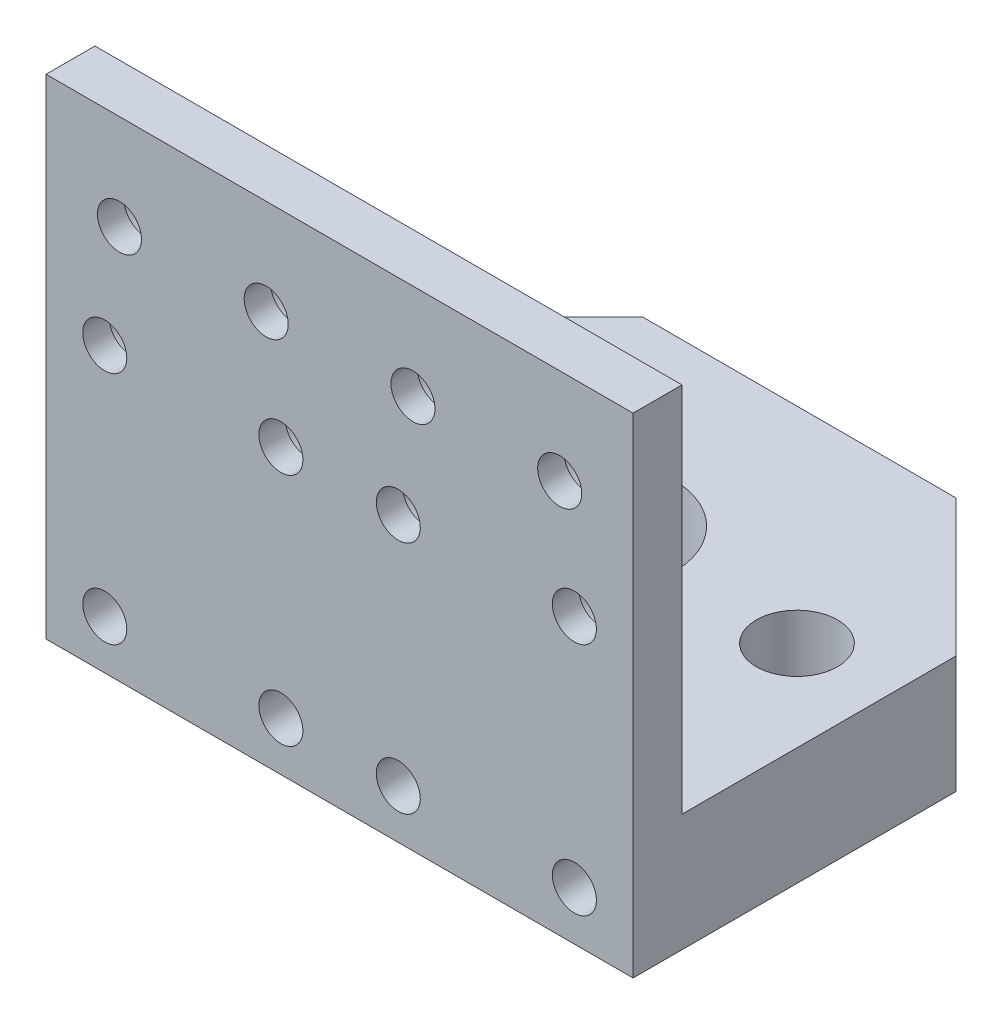
SolidWorks part; units mm, degrees
ref_plane "Front Plane" through (0, 0, 0) normal (0, 0, 1) x (1, 0, 0)
ref_plane "Top Plane" through (0, 0, 0) normal (0, 1, 0) x (1, 0, 0)
ref_plane "Right Plane" through (0, 0, 0) normal (1, 0, 0) x (0, 0, -1)
sketch "Sketch2" plane through (0, 0, 0) normal (1, 0, 0) x (0, 0, -1)
  line L23 (15.5, -57) -> (10.5, -57)
  line L24 (15.5, -57) -> (15.5, -7)
  line L25 (15.5, -7) -> (10.5, -7)
  line L26 (10.5, -57) -> (10.5, -7)
  dimension "D1" = 15.5
  dimension "D2" = 50
  dimension "D3" = 7
  dimension "D4" = 10.5
extrude "Boss-Extrude1" add sketch "Sketch2" along normal blind 30 and the other way blind 30 contours L24 L23 L26 L25
sketch "Sketch3" plane through (0, 0, -15.5) normal (0, 0, -1) x (-1, 0, 0)
  line L0 (30, -57) -> (30, -7) construction
  line L1 (-30, -57) -> (30, -57)
  line L2 (-30, -57) -> (-30, -45)
  line L3 (-30, -45) -> (30, -45)
  line L4 (30, -57) -> (30, -45)
  dimension "D1" = 12
extrude "Boss-Extrude2" add sketch "Sketch3" along normal blind 42
sketch "Sketch4" plane through (0, 0, -10.5) normal (0, 0, 1) x (1, 0, 0)
  line L0 (-30, -57) -> (-30, -7) construction
  line L1 (-30, -7) -> (30, -7) construction
  circle A0 centre (-22.5, -16.75) radius 2.25
  circle A1 centre (-7.5, -16.75) radius 2.25
  circle A2 centre (7.5, -16.75) radius 2.25
  circle A3 centre (22.5, -16.75) radius 2.25
  dimension "D1" = 4.5
  dimension "D2" = 7.5
  dimension "D3" = 9.75
  dimension "D5" = 15
  dimension "D4" = 4
extrude "Cut-Extrude1" cut sketch "Sketch4" against normal up to next
sketch "Sketch6" plane through (0, 0, -15.5) normal (0, 0, -1) x (-1, 0, 0)
  circle A0 centre (-22.5, -16.75) radius 4
  circle A1 centre (-7.5, -16.75) radius 4
  circle A2 centre (7.5, -16.75) radius 4
  circle A3 centre (22.5, -16.75) radius 4
  dimension "D1" = 8
  dimension "D3" = 15
  dimension "D2" = 4
extrude "Cut-Extrude2" cut sketch "Sketch6" against normal blind 2.3
sketch "Sketch7" plane through (0, 0, -10.5) normal (0, 0, 1) x (1, 0, 0)
  line L0 (-30, -57) -> (30, -57) construction
  line L1 (-30, -57) -> (-30, -7) construction
  line L2 (0, -7) -> (0, -57) construction
  line L3 (-30, -7) -> (30, -7) construction
  circle A0 centre (-24, -52) radius 2.25
  circle A1 centre (-6, -52) radius 2.25
  circle A2 centre (-24, -28) radius 2.25
  circle A3 centre (-6, -28) radius 2.25
  circle A4 centre (6, -28) radius 2.25
  circle A5 centre (24, -28) radius 2.25
  circle A6 centre (6, -52) radius 2.25
  circle A7 centre (24, -52) radius 2.25
  dimension "D1" = 5
  dimension "D2" = 6
  dimension "D3" = 4.5
  dimension "D5" = 18
  dimension "D7" = 24
  dimension "D4" = 2
  dimension "D6" = 2
extrude "Cut-Extrude3" cut sketch "Sketch7" against normal up to surface (5 mm away) up to face at (22.5, -12.75, -15.5)
sketch "Sketch8" plane through (0, 0, -15.5) normal (0, 0, -1) x (-1, 0, 0)
  line L0 (0, -7) -> (0, -45) construction
  line L1 (30, -7) -> (-30, -7) construction
  line L2 (30, -45) -> (-30, -45) construction
  circle A0 centre (-24, -28) radius 4
  circle A1 centre (-6, -28) radius 4
  circle A2 centre (6, -28) radius 4
  circle A3 centre (24, -28) radius 4
  dimension "D1" = 8
  dimension "D3" = 18
  dimension "D2" = 2
extrude "Cut-Extrude4" cut sketch "Sketch8" against normal blind 2.3
sketch "Sketch9" plane through (0, -45, 0) normal (0, 1, 0) x (1, 0, 0)
  line L0 (0, 57.5) -> (0, 15.5) construction
  line L1 (-30, 57.5) -> (30, 57.5) construction
  line L2 (-30, 15.5) -> (30, 15.5) construction
  line L3 (-30, 36.5) -> (30, 36.5) construction
  line L4 (-30, 57.5) -> (-30, 15.5) construction
  line L5 (30, 57.5) -> (30, 15.5) construction
  circle A0 centre (0, 36.5) radius 8.15
  circle A1 centre (-20.75, 36.5) radius 4.15
  circle A2 centre (20.75, 36.5) radius 4.15
  dimension "D1" = 16.3
  dimension "D2" = 8.3
  dimension "D3" = 20.75
extrude "Cut-Extrude5" cut sketch "Sketch9" against normal blind 10
sketch "Sketch10" plane through (0, -55, 0) normal (0, 1, 0) x (1, 0, 0)
  circle A0 centre (0, 36.5) radius 7.5
  circle A1 centre (-20.75, 36.5) radius 3
  circle A2 centre (20.75, 36.5) radius 3
  dimension "D1" = 15
  dimension "D2" = 6
  dimension "D3" = 6
extrude "Cut-Extrude6" cut sketch "Sketch10" against normal up to next
chamfer "Chamfer1" distance 14 angle 45 2 edges at (-30, -51, -57.5) (30, -51, -57.5)
